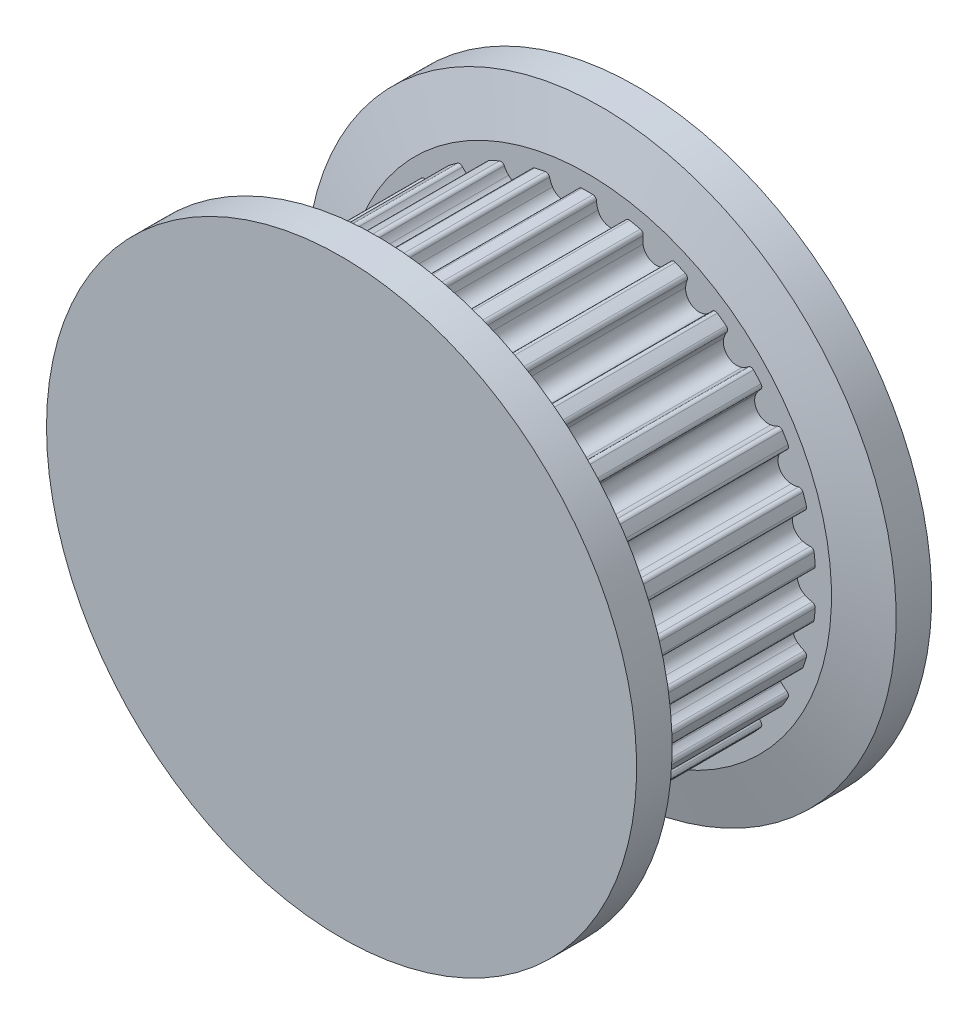
SolidWorks part; units mm, degrees
ref_plane "Front Plane" through (0, 0, 0) normal (0, 0, 1) x (1, 0, 0)
ref_plane "Top Plane" through (0, 0, 0) normal (0, 1, 0) x (1, 0, 0)
ref_plane "Right Plane" through (0, 0, 0) normal (1, 0, 0) x (0, 0, -1)
sketch "Teeth" plane through (0, 0, 0) normal (0, 0, 1) x (1, 0, 0)
  line L0 (0, 0) -> (9.7637, 0) construction
  line L1 (0, 0) -> (9.497, 0.9982) construction
  line L2 (0, 0) -> (9.497, -0.9982) construction
  arc A0 (9.265, -0.7494) -> (9.2444, -0.9716) centre (0, 0) cw
  arc A1 (8.8479, 0.4987) -> (9.1379, 0.589) centre (9.2867, -0.3999) cw
  arc A2 (8.8479, -0.4987) -> (9.1379, -0.589) centre (9.2867, 0.3999) ccw
  arc A3 (9.1379, -0.589) -> (9.265, -0.7494) centre (9.1155, -0.7373) cw
  arc A4 (8.9068, -2.6593) -> (8.8404, -2.8724) centre (0, 0) cw
  arc A5 (8.8157, -2.476) -> (8.9068, -2.6593) centre (8.763, -2.6164) cw
  arc A6 (8.8479, 0.4987) -> (8.8479, -0.4987) centre (9.0914, 0) ccw
  arc A7 (8.5509, -2.3274) -> (8.8157, -2.476) centre (9.1669, -1.5397) ccw
  arc A8 (8.7583, -1.3518) -> (8.5509, -2.3274) centre (8.8928, -1.8902) ccw
  arc A9 (8.7583, -1.3518) -> (9.0606, -1.3238) centre (9.0006, -2.322) cw
  arc A10 (9.0606, -1.3238) -> (9.2184, -1.1933) centre (9.0696, -1.174) ccw
  arc A11 (9.2184, -1.1933) -> (9.2444, -0.9716) centre (0, 0) ccw
  arc A12 (8.1592, -4.453) -> (8.05, -4.6476) centre (0, 0) cw
  arc A13 (8.1083, -4.2548) -> (8.1592, -4.453) centre (8.0276, -4.3812) cw
  arc A14 (7.8801, -4.0544) -> (8.1083, -4.2548) centre (8.6465, -3.4119) ccw
  circle A15 centre (0, 0) radius 9.5493 construction
  circle A16 centre (0, 0) radius 9.2953 construction
  arc A17 (8.2858, -3.1432) -> (7.8801, -4.0544) centre (8.3054, -3.6978) ccw
  arc A18 (8.2858, -3.1432) -> (8.5874, -3.1786) centre (8.3212, -4.1425) cw
  arc A19 (8.5874, -3.1786) -> (8.7688, -3.0838) centre (8.6273, -3.034) ccw
  arc A20 (8.7688, -3.0838) -> (8.8404, -2.8724) centre (0, 0) ccw
  arc A21 (7.0551, -6.0521) -> (6.9078, -6.2198) centre (0, 0) cw
  arc A22 (7.0465, -5.8476) -> (7.0551, -6.0521) centre (6.9412, -5.9545) cw
  circle A23 centre (0, 0) radius 9.9253 construction
  arc A24 (6.865, -5.6042) -> (7.0465, -5.8476) centre (7.7481, -5.1351) ccw
  arc A25 (7.4513, -4.7972) -> (6.865, -5.6042) centre (7.3551, -5.3438) ccw
  arc A26 (7.4513, -4.7972) -> (7.7389, -4.8946) centre (7.278, -5.7821) cw
  arc A27 (7.7389, -4.8946) -> (7.9361, -4.8396) centre (7.808, -4.7615) ccw
  arc A28 (7.9361, -4.8396) -> (8.05, -4.6476) centre (0, 0) ccw
  arc A29 (5.6426, -7.3867) -> (5.4636, -7.5201) centre (0, 0) cw
  arc A30 (5.6767, -7.1849) -> (5.6426, -7.3867) centre (5.5515, -7.2675) cw
  arc A31 (5.5498, -6.909) -> (5.6767, -7.1849) centre (6.5112, -6.6338) ccw
  arc A32 (6.291, -6.2416) -> (5.5498, -6.909) centre (6.0834, -6.7563) ccw
  arc A33 (6.291, -6.2416) -> (6.5521, -6.3966) centre (5.9168, -7.1689) cw
  arc A34 (6.5521, -6.3966) -> (6.7564, -6.3838) centre (6.6474, -6.2808) ccw
  arc A35 (6.7564, -6.3838) -> (6.9078, -6.2198) centre (0, 0) ccw
  arc A36 (3.9835, -8.3985) -> (3.7807, -8.4917) centre (0, 0) cw
  arc A37 (4.0589, -8.2081) -> (3.9835, -8.3985) centre (3.9192, -8.2629) cw
  arc A38 (3.9921, -7.9119) -> (4.0589, -8.2081) centre (4.9896, -7.8426) ccw
  arc A39 (4.8559, -7.4132) -> (3.9921, -7.9119) centre (4.5457, -7.8734) ccw
  arc A40 (4.8559, -7.4132) -> (5.079, -7.6191) centre (4.297, -8.2424) cw
  arc A41 (5.079, -7.6191) -> (5.2815, -7.6491) centre (5.1963, -7.5256) ccw
  arc A42 (5.2815, -7.6491) -> (5.4636, -7.5201) centre (0, 0) ccw
  arc A43 (2.1503, -9.0432) -> (1.9326, -9.0922) centre (0, 0) cw
  arc A44 (2.2636, -8.8726) -> (2.1503, -9.0432) centre (2.1156, -8.8972) cw
  arc A45 (2.2598, -8.569) -> (2.2636, -8.8726) centre (3.2501, -8.7086) ccw
  arc A46 (3.2085, -8.2608) -> (2.2598, -8.569) centre (2.8094, -8.6465) ccw
  arc A47 (3.2085, -8.2608) -> (3.3839, -8.5086) centre (2.4894, -8.9557) cw
  arc A48 (3.3839, -8.5086) -> (3.5758, -8.58) centre (3.5181, -8.4415) ccw
  arc A49 (3.5758, -8.58) -> (3.7807, -8.4917) centre (0, 0) ccw
  arc A50 (0.2232, -9.2926) -> (0, -9.2953) centre (0, 0) cw
  arc A51 (0.3694, -9.1494) -> (0.2232, -9.2926) centre (0.2196, -9.1427) cw
  arc A52 (0.4289, -8.8516) -> (0.3694, -9.1494) centre (1.3684, -9.194) ccw
  arc A53 (1.4208, -8.7473) -> (0.4289, -8.8516) centre (0.9503, -9.0416) ccw
  arc A54 (1.4208, -8.7473) -> (1.5409, -9.0262) centre (0.573, -9.2776) cw
  arc A55 (1.5409, -9.0262) -> (1.7138, -9.1359) centre (1.6861, -8.9885) ccw
  arc A56 (1.7138, -9.1359) -> (1.9326, -9.0922) centre (0, 0) ccw
  arc A57 (-1.7138, -9.1359) -> (-1.9326, -9.0922) centre (0, 0) cw
  arc A58 (-1.5409, -9.0262) -> (-1.7138, -9.1359) centre (-1.6861, -8.9885) cw
  arc A59 (-1.4208, -8.7473) -> (-1.5409, -9.0262) centre (-0.573, -9.2776) ccw
  arc A60 (-0.4289, -8.8516) -> (-1.4208, -8.7473) centre (-0.9503, -9.0416) ccw
  arc A61 (-0.4289, -8.8516) -> (-0.3694, -9.1494) centre (-1.3684, -9.194) cw
  arc A62 (-0.3694, -9.1494) -> (-0.2232, -9.2926) centre (-0.2196, -9.1427) ccw
  arc A63 (9.265, 0.7494) -> (9.2444, 0.9716) centre (0, 0) ccw
  arc A64 (-0.2232, -9.2926) -> (0, -9.2953) centre (0, 0) ccw
  arc A65 (9.1379, 0.589) -> (9.265, 0.7494) centre (9.1155, 0.7373) ccw
  arc A66 (-3.5758, -8.58) -> (-3.7807, -8.4917) centre (0, 0) cw
  arc A67 (-3.3839, -8.5086) -> (-3.5758, -8.58) centre (-3.5181, -8.4415) cw
  arc A68 (-3.2085, -8.2608) -> (-3.3839, -8.5086) centre (-2.4894, -8.9557) ccw
  arc A69 (-2.2598, -8.569) -> (-3.2085, -8.2608) centre (-2.8094, -8.6465) ccw
  arc A70 (-2.2598, -8.569) -> (-2.2636, -8.8726) centre (-3.2501, -8.7086) cw
  arc A71 (-2.2636, -8.8726) -> (-2.1503, -9.0432) centre (-2.1156, -8.8972) ccw
  arc A72 (-2.1503, -9.0432) -> (-1.9326, -9.0922) centre (0, 0) ccw
  arc A73 (-5.2815, -7.6491) -> (-5.4636, -7.5201) centre (0, 0) cw
  arc A74 (-5.079, -7.6191) -> (-5.2815, -7.6491) centre (-5.1963, -7.5256) cw
  arc A75 (-4.8559, -7.4132) -> (-5.079, -7.6191) centre (-4.297, -8.2424) ccw
  arc A76 (-3.9921, -7.9119) -> (-4.8559, -7.4132) centre (-4.5457, -7.8734) ccw
  arc A77 (-3.9921, -7.9119) -> (-4.0589, -8.2081) centre (-4.9896, -7.8426) cw
  arc A78 (-4.0589, -8.2081) -> (-3.9835, -8.3985) centre (-3.9192, -8.2629) ccw
  arc A79 (-3.9835, -8.3985) -> (-3.7807, -8.4917) centre (0, 0) ccw
  arc A80 (-6.7564, -6.3838) -> (-6.9078, -6.2198) centre (0, 0) cw
  arc A81 (-6.5521, -6.3966) -> (-6.7564, -6.3838) centre (-6.6474, -6.2808) cw
  arc A82 (-6.291, -6.2416) -> (-6.5521, -6.3966) centre (-5.9168, -7.1689) ccw
  arc A83 (-5.5498, -6.909) -> (-6.291, -6.2416) centre (-6.0834, -6.7563) ccw
  arc A84 (-5.5498, -6.909) -> (-5.6767, -7.1849) centre (-6.5112, -6.6338) cw
  arc A85 (-5.6767, -7.1849) -> (-5.6426, -7.3867) centre (-5.5515, -7.2675) ccw
  arc A86 (-5.6426, -7.3867) -> (-5.4636, -7.5201) centre (0, 0) ccw
  arc A87 (-7.9361, -4.8396) -> (-8.05, -4.6476) centre (0, 0) cw
  arc A88 (-7.7389, -4.8946) -> (-7.9361, -4.8396) centre (-7.808, -4.7615) cw
  arc A89 (-7.4513, -4.7972) -> (-7.7389, -4.8946) centre (-7.278, -5.7821) ccw
  arc A90 (-6.865, -5.6042) -> (-7.4513, -4.7972) centre (-7.3551, -5.3438) ccw
  arc A91 (-6.865, -5.6042) -> (-7.0465, -5.8476) centre (-7.7481, -5.1351) cw
  arc A92 (-7.0465, -5.8476) -> (-7.0551, -6.0521) centre (-6.9412, -5.9545) ccw
  arc A93 (-7.0551, -6.0521) -> (-6.9078, -6.2198) centre (0, 0) ccw
  arc A94 (-8.7688, -3.0838) -> (-8.8404, -2.8724) centre (0, 0) cw
  arc A95 (-8.5874, -3.1786) -> (-8.7688, -3.0838) centre (-8.6273, -3.034) cw
  arc A96 (-8.2858, -3.1432) -> (-8.5874, -3.1786) centre (-8.3212, -4.1425) ccw
  arc A97 (-7.8801, -4.0544) -> (-8.2858, -3.1432) centre (-8.3054, -3.6978) ccw
  arc A98 (-7.8801, -4.0544) -> (-8.1083, -4.2548) centre (-8.6465, -3.4119) cw
  arc A99 (-8.1083, -4.2548) -> (-8.1592, -4.453) centre (-8.0276, -4.3812) ccw
  arc A100 (-8.1592, -4.453) -> (-8.05, -4.6476) centre (0, 0) ccw
  arc A101 (-9.2184, -1.1933) -> (-9.2444, -0.9716) centre (0, 0) cw
  arc A102 (-9.0606, -1.3238) -> (-9.2184, -1.1933) centre (-9.0696, -1.174) cw
  arc A103 (-8.7583, -1.3518) -> (-9.0606, -1.3238) centre (-9.0006, -2.322) ccw
  arc A104 (-8.5509, -2.3274) -> (-8.7583, -1.3518) centre (-8.8928, -1.8902) ccw
  arc A105 (-8.5509, -2.3274) -> (-8.8157, -2.476) centre (-9.1669, -1.5397) cw
  arc A106 (-8.8157, -2.476) -> (-8.9068, -2.6593) centre (-8.763, -2.6164) ccw
  arc A107 (-8.9068, -2.6593) -> (-8.8404, -2.8724) centre (0, 0) ccw
  arc A108 (-9.265, 0.7494) -> (-9.2444, 0.9716) centre (0, 0) cw
  arc A109 (-9.1379, 0.589) -> (-9.265, 0.7494) centre (-9.1155, 0.7373) cw
  arc A110 (-8.8479, 0.4987) -> (-9.1379, 0.589) centre (-9.2867, -0.3999) ccw
  arc A111 (-8.8479, -0.4987) -> (-8.8479, 0.4987) centre (-9.0914, 0) ccw
  arc A112 (-8.8479, -0.4987) -> (-9.1379, -0.589) centre (-9.2867, 0.3999) cw
  arc A113 (-9.1379, -0.589) -> (-9.265, -0.7494) centre (-9.1155, -0.7373) ccw
  arc A114 (-9.265, -0.7494) -> (-9.2444, -0.9716) centre (0, 0) ccw
  arc A115 (-8.9068, 2.6593) -> (-8.8404, 2.8724) centre (0, 0) cw
  arc A116 (-8.8157, 2.476) -> (-8.9068, 2.6593) centre (-8.763, 2.6164) cw
  arc A117 (-8.5509, 2.3274) -> (-8.8157, 2.476) centre (-9.1669, 1.5397) ccw
  arc A118 (-8.7583, 1.3518) -> (-8.5509, 2.3274) centre (-8.8928, 1.8902) ccw
  arc A119 (-8.7583, 1.3518) -> (-9.0606, 1.3238) centre (-9.0006, 2.322) cw
  arc A120 (-9.0606, 1.3238) -> (-9.2184, 1.1933) centre (-9.0696, 1.174) ccw
  arc A121 (-9.2184, 1.1933) -> (-9.2444, 0.9716) centre (0, 0) ccw
  arc A122 (-8.1592, 4.453) -> (-8.05, 4.6476) centre (0, 0) cw
  arc A123 (-8.1083, 4.2548) -> (-8.1592, 4.453) centre (-8.0276, 4.3812) cw
  arc A124 (-7.8801, 4.0544) -> (-8.1083, 4.2548) centre (-8.6465, 3.4119) ccw
  arc A125 (-8.2858, 3.1432) -> (-7.8801, 4.0544) centre (-8.3054, 3.6978) ccw
  arc A126 (-8.2858, 3.1432) -> (-8.5874, 3.1786) centre (-8.3212, 4.1425) cw
  arc A127 (-8.5874, 3.1786) -> (-8.7688, 3.0838) centre (-8.6273, 3.034) ccw
  arc A128 (-8.7688, 3.0838) -> (-8.8404, 2.8724) centre (0, 0) ccw
  arc A129 (-7.0551, 6.0521) -> (-6.9078, 6.2198) centre (0, 0) cw
  arc A130 (-7.0465, 5.8476) -> (-7.0551, 6.0521) centre (-6.9412, 5.9545) cw
  arc A131 (-6.865, 5.6042) -> (-7.0465, 5.8476) centre (-7.7481, 5.1351) ccw
  arc A132 (-7.4513, 4.7972) -> (-6.865, 5.6042) centre (-7.3551, 5.3438) ccw
  arc A133 (-7.4513, 4.7972) -> (-7.7389, 4.8946) centre (-7.278, 5.7821) cw
  arc A134 (-7.7389, 4.8946) -> (-7.9361, 4.8396) centre (-7.808, 4.7615) ccw
  arc A135 (-7.9361, 4.8396) -> (-8.05, 4.6476) centre (0, 0) ccw
  arc A136 (-5.6426, 7.3867) -> (-5.4636, 7.5201) centre (0, 0) cw
  arc A137 (-5.6767, 7.1849) -> (-5.6426, 7.3867) centre (-5.5515, 7.2675) cw
  arc A138 (-5.5498, 6.909) -> (-5.6767, 7.1849) centre (-6.5112, 6.6338) ccw
  arc A139 (-6.291, 6.2416) -> (-5.5498, 6.909) centre (-6.0834, 6.7563) ccw
  arc A140 (-6.291, 6.2416) -> (-6.5521, 6.3966) centre (-5.9168, 7.1689) cw
  arc A141 (-6.5521, 6.3966) -> (-6.7564, 6.3838) centre (-6.6474, 6.2808) ccw
  arc A142 (-6.7564, 6.3838) -> (-6.9078, 6.2198) centre (0, 0) ccw
  arc A143 (-3.9835, 8.3985) -> (-3.7807, 8.4917) centre (0, 0) cw
  arc A144 (-4.0589, 8.2081) -> (-3.9835, 8.3985) centre (-3.9192, 8.2629) cw
  arc A145 (-3.9921, 7.9119) -> (-4.0589, 8.2081) centre (-4.9896, 7.8426) ccw
  arc A146 (-4.8559, 7.4132) -> (-3.9921, 7.9119) centre (-4.5457, 7.8734) ccw
  arc A147 (-4.8559, 7.4132) -> (-5.079, 7.6191) centre (-4.297, 8.2424) cw
  arc A148 (-5.079, 7.6191) -> (-5.2815, 7.6491) centre (-5.1963, 7.5256) ccw
  arc A149 (-5.2815, 7.6491) -> (-5.4636, 7.5201) centre (0, 0) ccw
  arc A150 (-2.1503, 9.0432) -> (-1.9326, 9.0922) centre (0, 0) cw
  arc A151 (-2.2636, 8.8726) -> (-2.1503, 9.0432) centre (-2.1156, 8.8972) cw
  arc A152 (-2.2598, 8.569) -> (-2.2636, 8.8726) centre (-3.2501, 8.7086) ccw
  arc A153 (-3.2085, 8.2608) -> (-2.2598, 8.569) centre (-2.8094, 8.6465) ccw
  arc A154 (-3.2085, 8.2608) -> (-3.3839, 8.5086) centre (-2.4894, 8.9557) cw
  arc A155 (-3.3839, 8.5086) -> (-3.5758, 8.58) centre (-3.5181, 8.4415) ccw
  arc A156 (-3.5758, 8.58) -> (-3.7807, 8.4917) centre (0, 0) ccw
  arc A157 (-0.2232, 9.2926) -> (0, 9.2953) centre (0, 0) cw
  arc A158 (-0.3694, 9.1494) -> (-0.2232, 9.2926) centre (-0.2196, 9.1427) cw
  arc A159 (-0.4289, 8.8516) -> (-0.3694, 9.1494) centre (-1.3684, 9.194) ccw
  arc A160 (-1.4208, 8.7473) -> (-0.4289, 8.8516) centre (-0.9503, 9.0416) ccw
  arc A161 (-1.4208, 8.7473) -> (-1.5409, 9.0262) centre (-0.573, 9.2776) cw
  arc A162 (-1.5409, 9.0262) -> (-1.7138, 9.1359) centre (-1.6861, 8.9885) ccw
  arc A163 (-1.7138, 9.1359) -> (-1.9326, 9.0922) centre (0, 0) ccw
  arc A164 (1.7138, 9.1359) -> (1.9326, 9.0922) centre (0, 0) cw
  arc A165 (1.5409, 9.0262) -> (1.7138, 9.1359) centre (1.6861, 8.9885) cw
  arc A166 (1.4208, 8.7473) -> (1.5409, 9.0262) centre (0.573, 9.2776) ccw
  arc A167 (0.4289, 8.8516) -> (1.4208, 8.7473) centre (0.9503, 9.0416) ccw
  arc A168 (0.4289, 8.8516) -> (0.3694, 9.1494) centre (1.3684, 9.194) cw
  arc A169 (0.3694, 9.1494) -> (0.2232, 9.2926) centre (0.2196, 9.1427) ccw
  arc A170 (0.2232, 9.2926) -> (0, 9.2953) centre (0, 0) ccw
  arc A171 (3.5758, 8.58) -> (3.7807, 8.4917) centre (0, 0) cw
  arc A172 (3.3839, 8.5086) -> (3.5758, 8.58) centre (3.5181, 8.4415) cw
  arc A173 (3.2085, 8.2608) -> (3.3839, 8.5086) centre (2.4894, 8.9557) ccw
  arc A174 (2.2598, 8.569) -> (3.2085, 8.2608) centre (2.8094, 8.6465) ccw
  arc A175 (2.2598, 8.569) -> (2.2636, 8.8726) centre (3.2501, 8.7086) cw
  arc A176 (2.2636, 8.8726) -> (2.1503, 9.0432) centre (2.1156, 8.8972) ccw
  arc A177 (2.1503, 9.0432) -> (1.9326, 9.0922) centre (0, 0) ccw
  arc A178 (5.2815, 7.6491) -> (5.4636, 7.5201) centre (0, 0) cw
  arc A179 (5.079, 7.6191) -> (5.2815, 7.6491) centre (5.1963, 7.5256) cw
  arc A180 (4.8559, 7.4132) -> (5.079, 7.6191) centre (4.297, 8.2424) ccw
  arc A181 (3.9921, 7.9119) -> (4.8559, 7.4132) centre (4.5457, 7.8734) ccw
  arc A182 (3.9921, 7.9119) -> (4.0589, 8.2081) centre (4.9896, 7.8426) cw
  arc A183 (4.0589, 8.2081) -> (3.9835, 8.3985) centre (3.9192, 8.2629) ccw
  arc A184 (3.9835, 8.3985) -> (3.7807, 8.4917) centre (0, 0) ccw
  arc A185 (6.7564, 6.3838) -> (6.9078, 6.2198) centre (0, 0) cw
  arc A186 (6.5521, 6.3966) -> (6.7564, 6.3838) centre (6.6474, 6.2808) cw
  arc A187 (6.291, 6.2416) -> (6.5521, 6.3966) centre (5.9168, 7.1689) ccw
  arc A188 (5.5498, 6.909) -> (6.291, 6.2416) centre (6.0834, 6.7563) ccw
  arc A189 (5.5498, 6.909) -> (5.6767, 7.1849) centre (6.5112, 6.6338) cw
  arc A190 (5.6767, 7.1849) -> (5.6426, 7.3867) centre (5.5515, 7.2675) ccw
  arc A191 (5.6426, 7.3867) -> (5.4636, 7.5201) centre (0, 0) ccw
  arc A192 (7.9361, 4.8396) -> (8.05, 4.6476) centre (0, 0) cw
  arc A193 (7.7389, 4.8946) -> (7.9361, 4.8396) centre (7.808, 4.7615) cw
  arc A194 (7.4513, 4.7972) -> (7.7389, 4.8946) centre (7.278, 5.7821) ccw
  arc A195 (6.865, 5.6042) -> (7.4513, 4.7972) centre (7.3551, 5.3438) ccw
  arc A196 (6.865, 5.6042) -> (7.0465, 5.8476) centre (7.7481, 5.1351) cw
  arc A197 (7.0465, 5.8476) -> (7.0551, 6.0521) centre (6.9412, 5.9545) ccw
  arc A198 (7.0551, 6.0521) -> (6.9078, 6.2198) centre (0, 0) ccw
  arc A199 (8.7688, 3.0838) -> (8.8404, 2.8724) centre (0, 0) cw
  arc A200 (8.5874, 3.1786) -> (8.7688, 3.0838) centre (8.6273, 3.034) cw
  arc A201 (8.2858, 3.1432) -> (8.5874, 3.1786) centre (8.3212, 4.1425) ccw
  arc A202 (7.8801, 4.0544) -> (8.2858, 3.1432) centre (8.3054, 3.6978) ccw
  arc A203 (7.8801, 4.0544) -> (8.1083, 4.2548) centre (8.6465, 3.4119) cw
  arc A204 (8.1083, 4.2548) -> (8.1592, 4.453) centre (8.0276, 4.3812) ccw
  arc A205 (8.1592, 4.453) -> (8.05, 4.6476) centre (0, 0) ccw
  arc A206 (9.2184, 1.1933) -> (9.2444, 0.9716) centre (0, 0) cw
  arc A207 (9.0606, 1.3238) -> (9.2184, 1.1933) centre (9.0696, 1.174) cw
  arc A208 (8.7583, 1.3518) -> (9.0606, 1.3238) centre (9.0006, 2.322) ccw
  arc A209 (8.5509, 2.3274) -> (8.7583, 1.3518) centre (8.8928, 1.8902) ccw
  arc A210 (8.5509, 2.3274) -> (8.8157, 2.476) centre (9.1669, 1.5397) cw
  arc A211 (8.8157, 2.476) -> (8.9068, 2.6593) centre (8.763, 2.6164) ccw
  arc A212 (8.9068, 2.6593) -> (8.8404, 2.8724) centre (0, 0) ccw
  point P2 (8.5364, 0)
  point P4 (9.5493, 0)
  point P45 (0, 0)
  point P48 (6.05, 0)
  point P53 (9.2953, 0)
  point P175 (0, 0)
  point P178 (9.2759, 0.6001)
  point P297 (0, 0)
  dimension "D1" = 0.63
  dimension "D2" = 1
  dimension "D3" = 0.4
  dimension "D5" = 2
  dimension "D6" = 0.254
  dimension "D8" = 30
  dimension "D4" = 0.555
  dimension "D7" = 0.15
extrude "Boss-Extrude1" add sketch "Teeth" along normal mid plane 8
sketch "Sketch3" plane through (0, 0, 0) normal (1, 0, 0) x (0, 0, -1)
  line L0 (4, 0) -> (-4, 0) construction
  line L1 (-4, 0) -> (-4, 9.9253)
  line L2 (-4, 0) -> (-6, 0)
  line L3 (-4, 9.9253) -> (-4.5559, 12)
  line L4 (-4.5559, 12) -> (-6, 12)
  line L5 (0, 0) -> (0, 9.9253) construction
  line L6 (-4, 9.9253) -> (4, 9.9253) construction
  line L7 (4, 0) -> (6, 0)
  line L8 (4, 9.9253) -> (4.5559, 12)
  line L9 (-6, 0) -> (-6, 12)
  line L10 (4.5559, 12) -> (6, 12)
  line L11 (6, 0) -> (6, 12)
  line L12 (4, 0) -> (4, 9.9253)
  point P5 (0, 0)
  dimension "D1" = 8
  dimension "D2" = 2
  dimension "D3" = 12
  dimension "D4" = 15
revolve "Revolve1" add sketch "Sketch3" angle 360 about L0
ref_axis "Axis" through (0, 0, -6.6) along (0, 0, 1)
